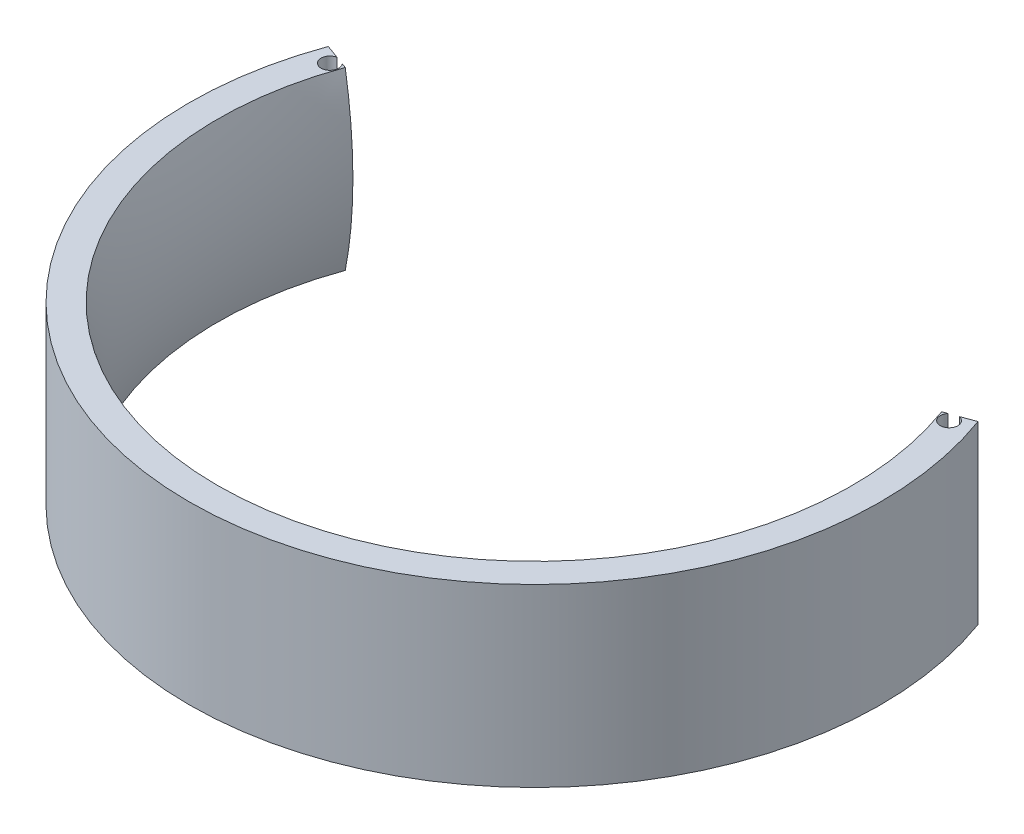
SolidWorks part; units mm, degrees
material "Silicon"
ref_plane "Front Plane" through (0, 0, 0) normal (0, 0, 1) x (1, 0, 0)
ref_plane "Top Plane" through (0, 0, 0) normal (0, 1, 0) x (1, 0, 0)
ref_plane "Right Plane" through (0, 0, 0) normal (1, 0, 0) x (0, 0, -1)
sketch "Sketch3" plane through (0, 0, 0) normal (0, 1, 0) x (1, 0, 0)
  line L0 (-35, 0) -> (35, 0) construction
  line L1 (0, 35) -> (0, -35) construction
  line L6 (-38, 5) -> (0, 0) construction
  line L7 (-38, 5) -> (-36, 5) construction
  line L8 (-38, 5) -> (-38, -5) construction
  line L9 (-38, -5) -> (-36, -5) construction
  line L10 (-36, 5) -> (-36, -5) construction
  line L11 (-38, 5) -> (-36, -5) construction
  line L12 (-38, -5) -> (-36, 5) construction
  line L13 (-5, -36) -> (5, -36) construction
  line L14 (-5, -36) -> (-5, -38) construction
  line L15 (-5, -38) -> (5, -38) construction
  line L16 (5, -36) -> (5, -38) construction
  line L17 (-5, -36) -> (5, -38) construction
  line L18 (-5, -38) -> (5, -36) construction
  line L19 (36, 5) -> (38, 5) construction
  line L20 (36, 5) -> (36, -5) construction
  line L21 (36, -5) -> (38, -5) construction
  line L22 (38, 5) -> (38, -5) construction
  line L23 (36, 5) -> (38, -5) construction
  line L24 (36, -5) -> (38, 5) construction
  line L25 (-38, 5) -> (-38.9915, 5.1305) construction
  line L26 (0, 0) -> (36.9558, 13.4508) construction
  line L27 (0, 0) -> (-36.9558, 13.4508) construction
  line L28 (36.9558, 13.4508) -> (32.8892, 11.9707) construction
  line L29 (-36.9558, 13.4508) -> (-32.8892, 11.9707) construction
  line L30 (-34.9225, 12.7108) -> (-35.2187, 11.897) construction
  line L31 (34.9225, 12.7108) -> (35.2187, 11.897) construction
  line L32 (-35.3924, 12.8818) -> (-34.4527, 12.5397) construction
  line L33 (34.4527, 12.5397) -> (35.3924, 12.8818) construction
  line L34 (-36.9558, 13.4508) -> (-35.3924, 12.8818)
  line L35 (-34.4527, 12.5397) -> (-32.8892, 11.9707)
  line L36 (32.8892, 11.9707) -> (34.4527, 12.5397)
  line L37 (35.3924, 12.8818) -> (36.9558, 13.4508)
  circle A0 centre (0, 0) radius 35 construction
  circle A1 centre (0, 0) radius 39.3275 construction
  circle A5 centre (-35.2187, 11.897) radius 1 construction
  circle A6 centre (35.2187, 11.897) radius 1 construction
  arc A7 (32.8892, 11.9707) -> (-32.8892, 11.9707) centre (0, 0) cw
  arc A8 (36.9558, 13.4508) -> (-36.9558, 13.4508) centre (0, 0) cw
  arc A9 (-35.3924, 12.8818) -> (-34.4527, 12.5397) centre (-35.2187, 11.897) ccw
  arc A10 (34.4527, 12.5397) -> (35.3924, 12.8818) centre (35.2187, 11.897) ccw
  point P7 (-37, 0)
  point P10 (-35, 0)
  point P14 (0, -37)
  point P19 (37, 0)
  point P35 (-34.9225, 12.7108)
  point P38 (34.9225, 12.7108)
  point P45 (0, -36)
  point P46 (0, -38)
  point P47 (0, -39.3275)
  point P54 (0, -35)
  dimension "D1" = 70
  dimension "D16" = 2
  dimension "D17" = 2
  dimension "D2" = 2
  dimension "D3" = 10
  dimension "D4" = 1
  dimension "D5" = 2
  dimension "D6" = 10
  dimension "D7" = 1
  dimension "D8" = 10
  dimension "D9" = 2
  dimension "D10" = 1
  dimension "D11" = 1
  dimension "D12" = 70
  dimension "D13" = 70
  dimension "D14" = 1
  dimension "D15" = 1
extrude "Fundametal Dimensions" add sketch "Sketch3" along normal blind 10 and the other way blind 10
sketch "Sketch9" plane through (0, 0, 0) normal (1, 0, 0) x (0, 0, -1)
  line L0 (-35, -10) -> (-35, 10) construction
  line L1 (-38, -5) -> (-38, 5) construction
  line L2 (-36, -5) -> (-36, 5) construction
  line L3 (-39.3275, -10) -> (-39.3275, 10) construction
  line L4 (-39.3275, 10) -> (-35, 10) construction
  line L5 (-38, 5) -> (-36, 5) construction
  line L6 (-38, -5) -> (-36, -5) construction
  line L7 (-39.3275, -10) -> (-35, -10) construction
  line L8 (-36, 5) -> (-35, 5) construction
  line L9 (-36, -5) -> (-35, -5) construction
  line L10 (-36.1, 10) -> (-35, 10)
  line L11 (-35, 10) -> (-35, 5)
  line L12 (-36.1, -10) -> (-35, -10)
  line L13 (-35, -10) -> (-35, -5)
  line L14 (0, -20) -> (0, 20) construction
  arc A0 (-35, 5) -> (-35, -5) centre (-69.641, 0) cw construction
  arc A1 (-34.641, 0) -> (-36.1, 10) centre (-69.641, 0) ccw construction
  arc A2 (-34.641, 0) -> (-36.1, -10) centre (-69.641, 0) cw construction
  arc A3 (-36.1, 10) -> (-35, 5) centre (-69.641, 0) cw
  arc A4 (-35, -5) -> (-36.1, -10) centre (-69.641, 0) cw
  point P4 (-35, 0)
  point P9 (-38, 0)
  point P14 (-36, 0)
  point P19 (-39.3275, 0)
  point P25 (-34.641, 0)
  point P32 (0, 0)
  dimension "D1" = 10
  dimension "D3" = 35
  dimension "D2" = 20
  dimension "D4" = 40
revolve "Round Inside Cut" cut sketch "Sketch9" angle 110 about L14 other way angle 110
sketch "Sketch10" plane through (0, 0, 0) normal (1, 0, 0) x (0, 0, -1)
  line L0 (-35, 5) -> (-35, -5)
  arc A0 (-35, 5) -> (-35, -5) centre (-69.641, 0) cw
  arc A1 (-35, -5) -> (-35, 5) centre (-69.641, 0) ccw construction
  dimension "D1" = 35
revolve "Round Inside Extruded" add sketch "Sketch10" angle 110 about L14 other way angle 110
equation "\"Ankle Diameter\"= 70mm"
equation "\"D1@Sketch3\"=\"Ankle Diameter\""
equation "\"Padding Thickness\"= 1mm"
equation "\"D4@Sketch3\"=\"Padding Thickness\""
equation "\"D7@Sketch3\"=\"Padding Thickness\""
equation "\"D10@Sketch3\"=\"Padding Thickness\""
equation "\"D11@Sketch3\"=\"Padding Thickness\""
equation "\"Total Width\"= 40mm"
equation "\"Band Width\"= 20mm"
equation "\"Gap for Strap Arc Angle\"= 140mm"
equation "\"D12@Sketch3\"=\"Gap for Strap Arc Angle\" / 2"
equation "\"D13@Sketch3\"=\"Gap for Strap Arc Angle\" / 2"
equation "\"Strap Holder Diameter\"= 2mm"
equation "\"Strap Thickness\"= 1mm"
equation "\"D14@Sketch3\"=\"Strap Thickness\""
equation "\"D15@Sketch3\"=\"Strap Thickness\""
equation "\"D16@Sketch3\"=\"Strap Holder Diameter\""
equation "\"D17@Sketch3\"=\"Strap Holder Diameter\""
equation "\"D1@Fundametal Dimensions\" = \"Band Width\" / 2"
equation "\"D2@Fundametal Dimensions\" = \"Band Width\" / 2"
equation "\"D2@Sketch9\"=\"Band Width\""
equation "\"D3@Sketch9\"=\"Ankle Diameter\" / 2"
equation "\"D4@Sketch9\"=\"Total Width\""
equation "\"D1@Round Inside Cut\" = 180 - \"Gap for Strap Arc Angle\" / 2"
equation "\"D2@Round Inside Cut\"=180 - \"Gap for Strap Arc Angle\" / 2"
equation "\"D1@Sketch10\"=\"Ankle Diameter\" / 2"
equation "\"D1@Round Inside Extruded\" = 180 - \"Gap for Strap Arc Angle\" / 2"
equation "\"D2@Round Inside Extruded\"=180 - \"Gap for Strap Arc Angle\" / 2"
